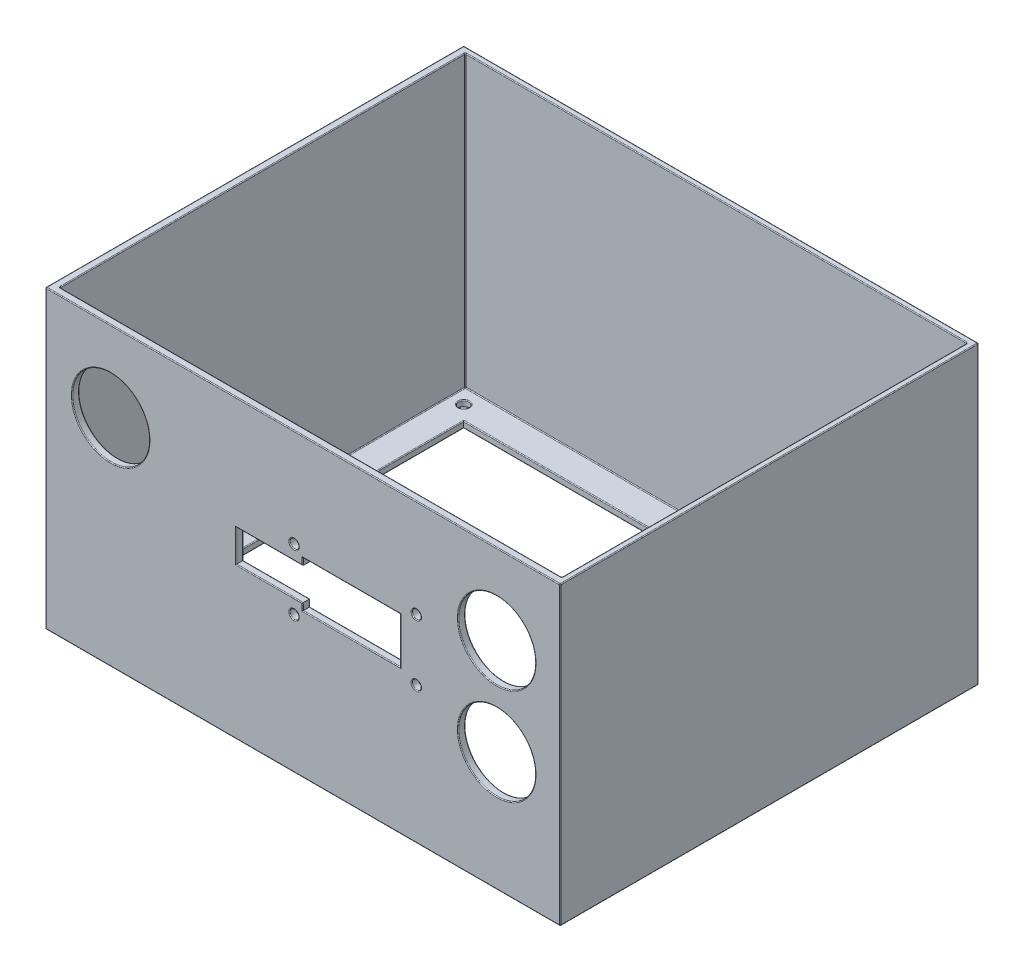
SolidWorks part; units mm, degrees
ref_plane "Front Plane" through (0, 0, 0) normal (0, 0, 1) x (1, 0, 0)
ref_plane "Top Plane" through (0, 0, 0) normal (0, 1, 0) x (1, 0, 0)
ref_plane "Right Plane" through (0, 0, 0) normal (1, 0, 0) x (0, 0, -1)
sketch "Sketch1" plane through (0, 0, 0) normal (0, 1, 0) x (1, 0, 0)
  line L1 (-0.2428, 129.7572) -> (159.7572, 129.7572)
  line L2 (159.7572, 129.7572) -> (159.7572, -0.2428)
  line L3 (-0.2428, -0.2428) -> (159.7572, -0.2428)
  line L4 (-0.2428, 129.7572) -> (-0.2428, -0.2428)
  line L15 (2, 128) -> (2, 2)
  line L16 (2, 2) -> (158, 2)
  line L17 (158, 128) -> (158, 2)
  line L19 (2, 128) -> (158, 128)
  dimension "D1" = 160
  dimension "D2" = 130
extrude "Boss-Extrude3" add sketch "Sketch1" against normal blind 90 contours L1 L4 L3 L2 L15 L19 L17 L16
ref_plane "Plane1" through (0, -90, 0) normal (0, -1, 0) x (-1, 0, 0)
sketch "Sketch2" plane through (0, -90, 0) normal (0, -1, 0) x (-1, 0, 0)
  line L0 (-79.7572, 84.7572) -> (-58.544, 63.544) construction
  line L1 (-159.7572, -0.2428) -> (0.2428, -0.2428) construction
  line L2 (-159.7572, -0.2428) -> (-159.7572, 129.7572) construction
  line L3 (-159.7572, 129.7572) -> (0.2428, 129.7572) construction
  line L4 (0.2428, -0.2428) -> (0.2428, 129.7572) construction
  line L5 (-79.7572, 84.7572) -> (-100.9704, 105.9704) construction
  line L6 (-79.7572, 129.7572) -> (-79.7572, -0.2428) construction
  line L7 (-96.7572, 30.7572) -> (-79.7572, 30.7572) construction
  line L8 (-79.7572, 30.7572) -> (-62.7572, 30.7572) construction
  line L9 (-157.7572, 1.7572) -> (-157.7572, 127.7572)
  line L10 (-157.7572, 127.7572) -> (-1.7572, 127.7572)
  line L11 (-1.7572, 1.7572) -> (-1.7572, 127.7572)
  line L12 (-157.7572, 1.7572) -> (-1.7572, 1.7572)
  line L13 (-159.7572, -0.2428) -> (0.2428, -0.2428)
  line L14 (0.2428, -0.2428) -> (0.2428, 129.7572)
  line L15 (-159.7572, 129.7572) -> (0.2428, 129.7572)
  line L16 (-159.7572, -0.2428) -> (-159.7572, 129.7572)
  line L17 (-148.7572, 1.7572) -> (-148.7572, 10.7572) construction
  line L18 (-148.7572, 10.7572) -> (-157.7572, 10.7572) construction
  line L19 (-10.7572, 1.7572) -> (-10.7572, 10.7572) construction
  line L20 (-10.7572, 10.7572) -> (-1.7572, 10.7572) construction
  line L21 (-157.7572, 118.7572) -> (-148.7572, 118.7572) construction
  line L22 (-148.7572, 118.7572) -> (-148.7572, 127.7572) construction
  line L23 (-1.7572, 118.7572) -> (-10.7572, 118.7572) construction
  line L24 (-10.7572, 118.7572) -> (-10.7572, 127.7572) construction
  line L25 (-157.7572, 1.7572) -> (-148.7572, 10.7572) construction
  line L26 (-10.7572, 10.7572) -> (-1.7572, 1.7572) construction
  line L27 (-148.7572, 118.7572) -> (-157.7572, 127.7572) construction
  line L28 (-10.7572, 118.7572) -> (-1.7572, 127.7572) construction
  line L29 (-148.7572, 10.7572) -> (-10.7572, 10.7572)
  line L30 (-10.7572, 10.7572) -> (-10.7572, 118.7572)
  line L31 (-10.7572, 118.7572) -> (-148.7572, 118.7572)
  line L32 (-148.7572, 118.7572) -> (-148.7572, 10.7572)
  circle A0 centre (-79.7572, 84.7572) radius 19.5 construction
  circle A1 centre (-100.9704, 105.9704) radius 1.75
  circle A2 centre (-58.544, 63.544) radius 1.75
  circle A3 centre (-96.7572, 30.7572) radius 12 construction
  circle A4 centre (-62.7572, 30.7572) radius 12 construction
  circle A5 centre (-153.2572, 123.2572) radius 1.625
  circle A6 centre (-6.2572, 123.2572) radius 1.625
  circle A7 centre (-6.2572, 6.2572) radius 1.625
  circle A8 centre (-153.2572, 6.2572) radius 1.625
  point P47 (0, 0)
  point P48 (-80, 75.0643)
  point P49 (-80, 82.7418)
  point P50 (0, 0)
  dimension "D1" = 39
  dimension "D4" = 3.5
  dimension "D5" = 24
  dimension "D10" = 3.25
  dimension "D2" = 45
  dimension "D3" = 30
  dimension "D6" = 17
  dimension "D7" = 2
  dimension "D9" = 9
  dimension "D11" = 20
  dimension "D12" = 45
  dimension "D8" = 2
extrude "Boss-Extrude4" add sketch "Sketch2" along normal blind 2 contours L9 L12 L11 L10 A8 A7 A6 A5 L32 L31 L30 L29 | L16 L13 L14 L15 L12 L9 L10 L11 region at (155.7519, -90, -64.7572) region at (159.5511, -90, -64.7572)
ref_plane "Plane2" through (0, 0, 0.2428) normal (0, 0, 1) x (1, 0, 0)
sketch "Sketch3" plane through (0, 0, 0.2428) normal (0, 0, 1) x (1, 0, 0)
  line L0 (0, -25) -> (160, -25) construction
  line L1 (140, -25) -> (140, -55) construction
  line L2 (77, -30.5) -> (115, -30.5) construction
  line L3 (77, -30.5) -> (77, -49.5) construction
  line L4 (77, -49.5) -> (115, -49.5) construction
  line L5 (115, -30.5) -> (115, -49.5) construction
  line L6 (96, -49.5) -> (96, -30.5) construction
  line L7 (77, -40) -> (115, -40) construction
  line L8 (59, -45) -> (79.7, -45)
  line L9 (59, -45) -> (59, -35)
  line L10 (59, -35) -> (79.7, -35)
  line L11 (69.35, -35) -> (69.35, -45) construction
  line L12 (59, -40) -> (77, -40) construction
  line L13 (140, -40) -> (0, -40) construction
  line L14 (0, -25) -> (0, -80)
  line L15 (0, -80) -> (160, -80)
  line L16 (160, -80) -> (160, -25)
  line L17 (160, -25) -> (160, 0)
  line L18 (160, 0) -> (0, 0)
  line L19 (0, 0) -> (0, -25)
  line L20 (140, -25) -> (140, 0) construction
  line L21 (140, -55) -> (140, -80) construction
  line L22 (94.85, -32.85) -> (94.85, -30.5) construction
  line L23 (94.85, -47.15) -> (94.85, -49.5) construction
  line L24 (79.7, -32.85) -> (110, -32.85)
  line L25 (79.7, -47.15) -> (110, -47.15)
  line L26 (110, -32.85) -> (110, -47.15)
  line L27 (79.7, -47.15) -> (79.7, -35)
  line L28 (79.7, -45) -> (79.7, -32.85)
  circle A0 centre (140, -25) radius 12
  circle A1 centre (20, -25) radius 12
  circle A2 centre (115, -49.5) radius 1.4
  circle A3 centre (77, -49.5) radius 1.4
  circle A4 centre (77, -30.5) radius 1.4
  circle A5 centre (115, -30.5) radius 1.4
  circle A6 centre (140, -55) radius 12
  point P8 (69.35, -40)
  point P11 (96, -40)
  point P45 (-2.4157, -93.6109)
  point P46 (4.1397, -83.3608)
  point P47 (0, 0)
  dimension "D1" = 24
  dimension "D7" = 2.8
  dimension "D2" = 20
  dimension "D3" = 20
  dimension "D4" = 38
  dimension "D5" = 19
  dimension "D6" = 10
  dimension "D8" = 30
  dimension "D9" = 25
  dimension "D10" = 160
  dimension "D11" = 80
  dimension "D12" = 18
  dimension "D13" = 30.3
  dimension "D14" = 14.3
  dimension "D15" = 5
extrude "Cut-Extrude1" cut sketch "Sketch3" against normal blind 10 contours A6 | A0 | A5 | A2 | L28 L27 L25 L26 L24 | L8 L27 L10 L9 | A3 | A4 | A1 region at (69.35, -40, 0.2428) region at (94.85, -40, 0.2428) region at (140, -25, 0.2428) region at (20, -25, 0.2428) region at (115, -49.5, 0.2428) region at (77, -49.5, 0.2428) region at (77, -30.5, 0.2428) region at (115, -30.5, 0.2428) region at (140, -55, 0.2428)
fillet "Fillet2" radius 0.25 70 edges at (-0.2428, -46, -129.7572) (159.7572, -46, -129.7572) (159.7572, -46, 0.2428) (-0.2428, -46, 0.2428) (-0.2428, 0, -64.7572) (79.7572, 0, -129.7572) (159.7572, 0, -64.7572) (79.7572, 0, 0.2428) (80, 0, -2) (158, 0, -65) (80, 0, -128) (2, 0, -65) (-0.2428, -92, -64.7572) (79.7572, -92, -129.7572) (159.7572, -92, -64.7572) (110, -40, 0.2428) (94.85, -32.85, 0.2428) (79.7, -46.075, 0.2428) (69.35, -35, 0.2428) (59, -40, 0.2428) (69.35, -45, 0.2428) (79.7, -33.925, 0.2428) (94.85, -47.15, 0.2428) (79.7572, -92, 0.2428) (152, -55, 0.2428) (32, -25, 0.2428) (78.4, -30.5, 0.2428) (78.4, -49.5, 0.2428) (152, -25, 0.2428) (116.4, -30.5, 0.2428) (116.4, -49.5, 0.2428) (79.7572, -92, -10.7572) (10.7572, -92, -64.7572) (79.7572, -92, -118.7572) (148.7572, -92, -64.7572) (153.2572, -92, -124.8822) (6.2572, -92, -124.8822) (6.2572, -92, -7.8822) (153.2572, -92, -7.8822) (158, -90, -65) (80, -90, -2) (2, -90, -65) (80, -90, -128) (153.2572, -90, -7.8822) (6.2572, -90, -7.8822) (6.2572, -90, -124.8822) (153.2572, -90, -124.8822) (79.7572, -90, -118.7572) (10.7572, -90, -64.7572) (79.7572, -90, -10.7572) (148.7572, -90, -64.7572) (2, -45, -128) (158, -45, -128) (69.35, -45, -2) (59, -40, -2) (69.35, -35, -2) (79.7, -46.075, -2) (94.85, -32.85, -2) (110, -40, -2) (94.85, -47.15, -2) (79.7, -33.925, -2) (116.4, -49.5, -2) (116.4, -30.5, -2) (152, -25, -2) (78.4, -49.5, -2) (78.4, -30.5, -2) (32, -25, -2) (152, -55, -2) (2, -45, -2) (158, -45, -2)
